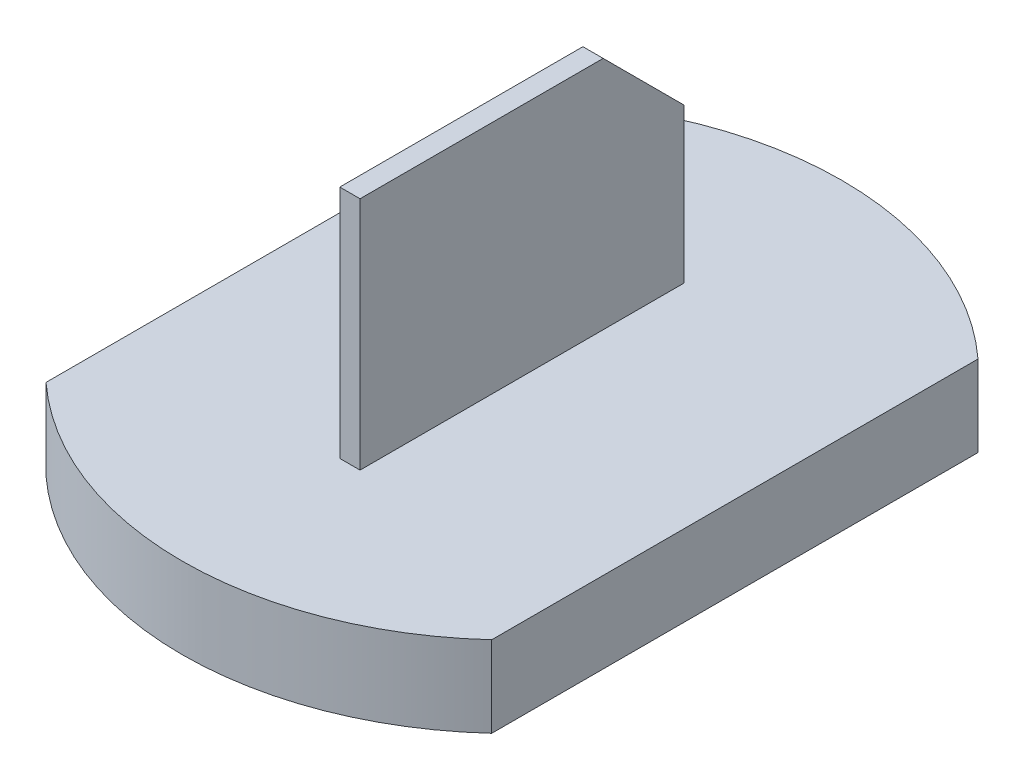
SolidWorks part; units mm, degrees
ref_plane "Front Plane" through (0, 0, 0) normal (0, 0, 1) x (1, 0, 0)
ref_plane "Top Plane" through (0, 0, 0) normal (0, 1, 0) x (1, 0, 0)
ref_plane "Right Plane" through (0, 0, 0) normal (1, 0, 0) x (0, 0, -1)
sketch "Sketch1" plane through (0, 0, 0) normal (0, 1, 0) x (1, 0, 0)
  line L1 (50.8, 38.1) -> (-50.8, 38.1)
  line L2 (50.8, 38.1) -> (50.8, -38.1)
  line L3 (50.8, -38.1) -> (-50.8, -38.1)
  line L4 (-50.8, 38.1) -> (-50.8, -38.1)
  line L5 (50.8, 38.1) -> (-50.8, -38.1) construction
  line L6 (50.8, -38.1) -> (-50.8, 38.1) construction
  line L7 (-1.5875, 25.4) -> (1.5875, 25.4)
  line L8 (-1.5875, 25.4) -> (-1.5875, -25.4)
  line L9 (-1.5875, -25.4) -> (1.5875, -25.4)
  line L10 (1.5875, 25.4) -> (1.5875, -25.4)
  line L11 (-1.5875, 25.4) -> (1.5875, -25.4) construction
  line L12 (-1.5875, -25.4) -> (1.5875, 25.4) construction
  line L13 (-34.925, -38.1) -> (-50.8, -38.1)
  line L14 (-34.925, -38.1) -> (-34.925, 38.1)
  line L15 (-34.925, 38.1) -> (-50.8, 38.1)
  line L16 (-50.8, -38.1) -> (-50.8, 38.1)
  line L17 (-34.925, -38.1) -> (-50.8, 38.1) construction
  line L18 (-34.925, 38.1) -> (-50.8, -38.1) construction
  line L19 (34.925, 38.1) -> (50.8, 38.1)
  line L20 (34.925, 38.1) -> (34.925, -38.1)
  line L21 (34.925, -38.1) -> (50.8, -38.1)
  line L22 (50.8, 38.1) -> (50.8, -38.1)
  line L23 (34.925, 38.1) -> (50.8, -38.1) construction
  line L24 (34.925, -38.1) -> (50.8, 38.1) construction
  circle A2 centre (0, 0) radius 51.6853
  point P0 (0, 0)
  point P6 (0, 0)
  point P12 (42.8625, 0)
  point P13 (-42.8625, 0)
  dimension "D1" = 76.2
  dimension "D2" = 101.6
  dimension "D3" = 3.175
  dimension "D4" = 50.8
  dimension "D5" = 15.875
  dimension "D6" = 76.2
  dimension "D7" = 15.875
  dimension "D8" = 76.2
extrude "Boss-Extrude1" add sketch "Sketch1" along normal mid plane 12.7 contours L3 L1 L7 L10 L9 L8 | L1 A2 | L3 A2 region at (33.8913, 0, 0) region at (0, 0, -43.6004) region at (0, 0, 43.6004)
extrude "Boss-Extrude2" add sketch "Sketch1<3>" along normal blind 43.18 and the other way up to surface (6.35 mm away) contours L8 L9 L10 L7 other way up to face at (0, -6.35, 0)
sketch "Sketch1<3>" plane through (0, 0, 0) normal (0, 1, 0) x (1, 0, 0) same geometry as "Sketch1"
chamfer "Chamfer1" distance 12.7 angle 45 1 edges at (0, 43.18, -25.4)
